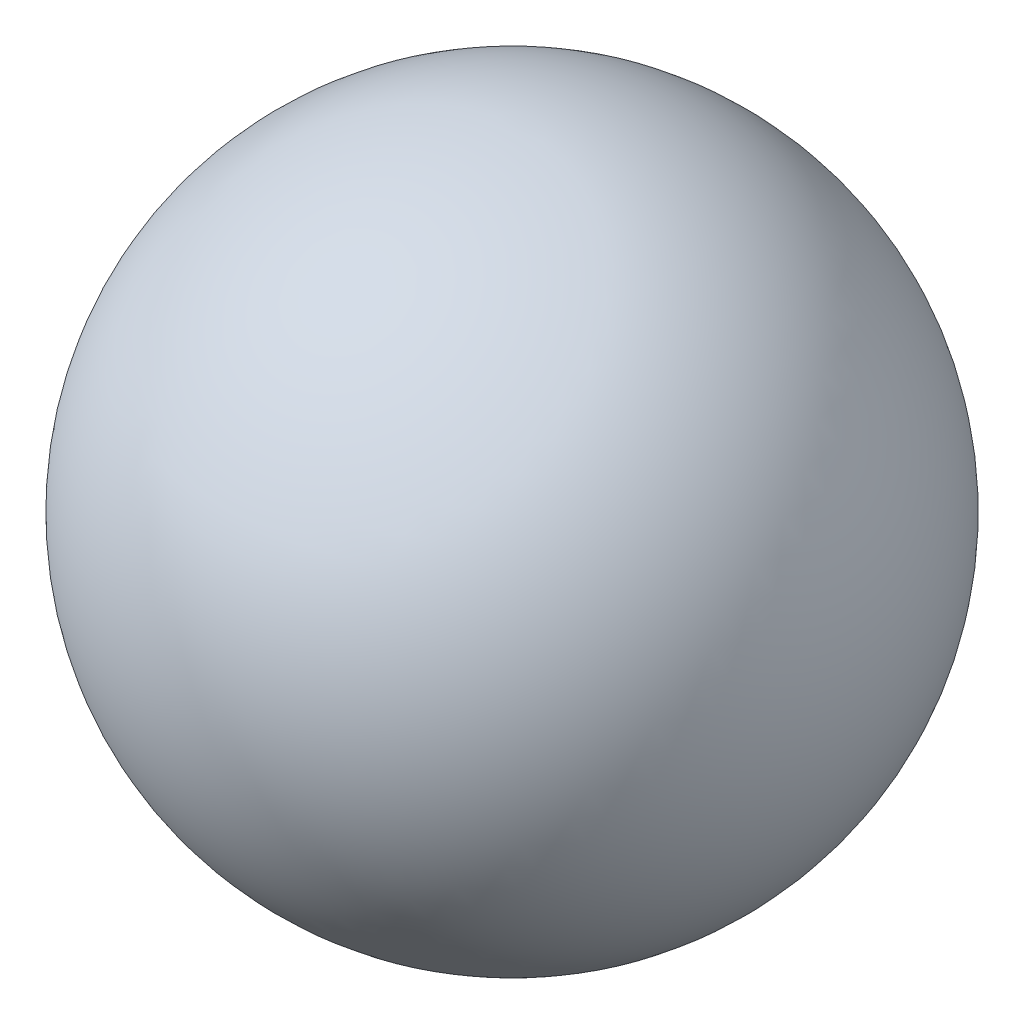
SolidWorks part; units mm, degrees
material "Parachute"
ref_plane "Front Plane" through (0, 0, 0) normal (0, 0, 1) x (1, 0, 0)
ref_plane "Top Plane" through (0, 0, 0) normal (0, 1, 0) x (1, 0, 0)
ref_plane "Right Plane" through (0, 0, 0) normal (1, 0, 0) x (0, 0, -1)
sketch "Sketch1" plane through (0, 0, 0) normal (0, 0, 1) x (1, 0, 0)
  line L0 (0, 50.8) -> (0, -50.8)
  arc A0 (0, 50.8) -> (0, -50.8) centre (0, 0) cw
  dimension "D1" = 50.8
revolve "Revolve1" add sketch "Sketch1" angle 360 about L0
